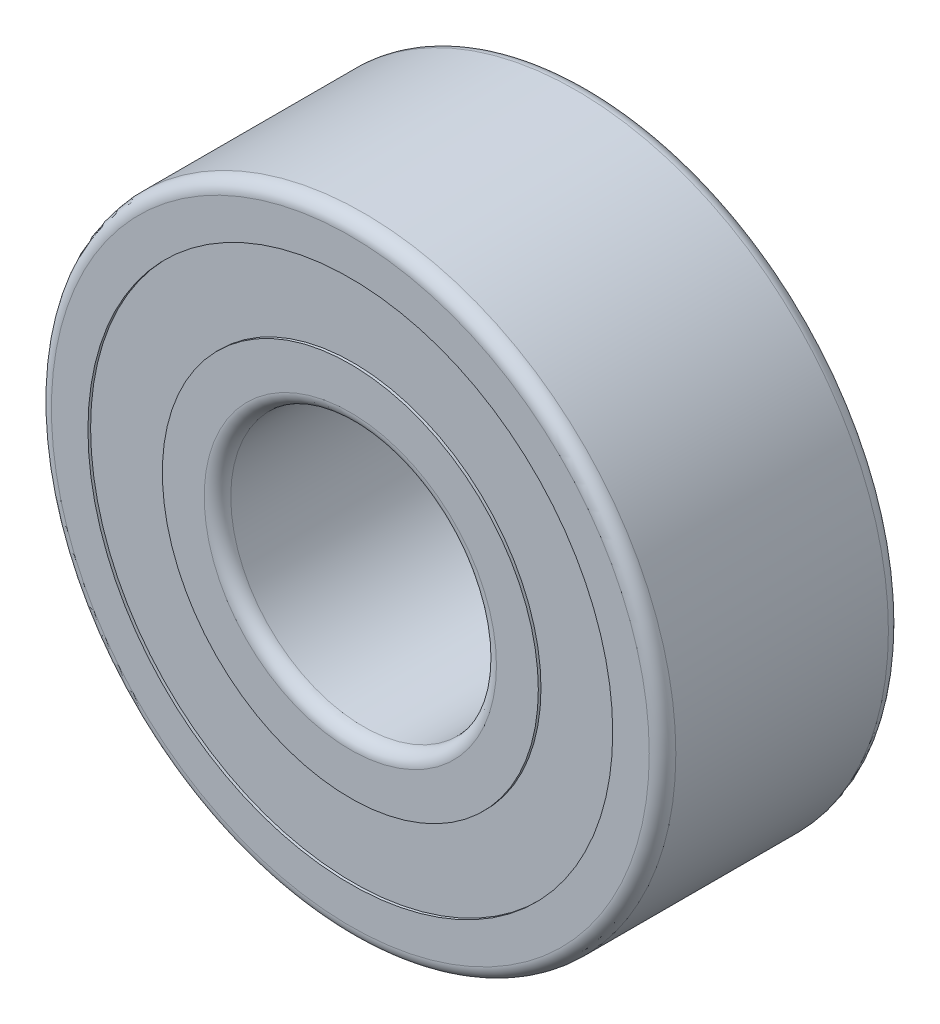
SolidWorks part; units mm, degrees
material "1.7033 (34Cr4)"
ref_plane "Спереди" through (0, 0, 0) normal (0, 0, 1) x (1, 0, 0)
ref_plane "Сверху" through (0, 0, 0) normal (0, 1, 0) x (1, 0, 0)
ref_plane "Справа" through (0, 0, 0) normal (1, 0, 0) x (0, 0, -1)
sketch "Эскиз1" plane through (0, 0, 0) normal (0, 0, 1) x (1, 0, 0)
  circle A0 centre (0, 0) radius 23.5
  circle A1 centre (0, 0) radius 10
  dimension "D1" = 47
  dimension "D2" = 20
extrude "Бобышка-Вытянуть1" add sketch "Эскиз1" along normal blind 18
fillet "Скругление1" radius 1 4 edges at (10, 0, 0) (10, 0, 18) (23.5, 0, 0) (23.5, 0, 18)
sketch "Эскиз2" plane through (0, 0, 18) normal (0, 0, 1) x (1, 0, 0)
  circle A0 centre (0, 0) radius 19.75
  circle A1 centre (0, 0) radius 14.15
  dimension "D1" = 28.3
  dimension "D2" = 39.5
extrude "Вырез-Вытянуть1" cut sketch "Эскиз2" against normal blind 0.2
extrude "Вырез-Вытянуть2" cut sketch "Эскиз2<3>" along normal blind 0.2 from offset 18 offset against normal yes
sketch "Эскиз2<3>" plane through (0, 0, 18) normal (0, 0, 1) x (1, 0, 0) same geometry as "Эскиз2"
